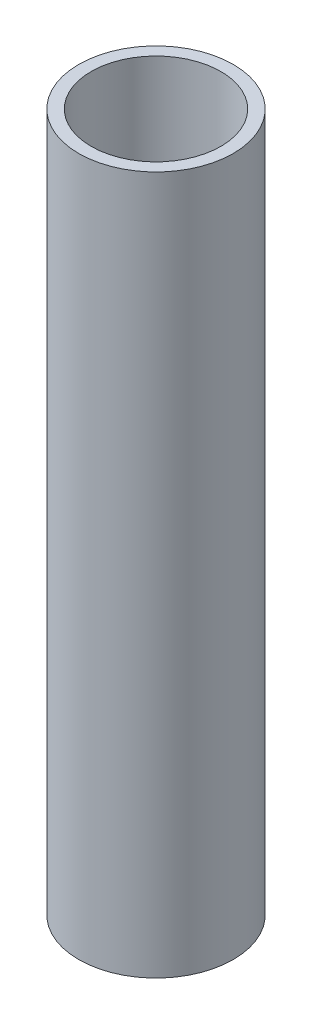
SolidWorks part; units mm, degrees
ref_plane "Front Plane" through (0, 0, 0) normal (0, 0, 1) x (1, 0, 0)
ref_plane "Top Plane" through (0, 0, 0) normal (0, 1, 0) x (1, 0, 0)
ref_plane "Right Plane" through (0, 0, 0) normal (1, 0, 0) x (0, 0, -1)
sketch "Sketch1" plane through (0, 0, 0) normal (0, 1, 0) x (1, 0, 0)
  circle A0 centre (0, 0) radius 12.5
  circle A1 centre (0, 0) radius 10.5
  dimension "D1" = 25
  dimension "D2" = 21
extrude "Boss-Extrude1" add sketch "Sketch1" along normal blind 113
equation "\"cf_tube_outer_diameter\" = 25mm"
equation "\"cf_tube_inner_diameter\" = 21mm"
equation "\"mid_plate_mid_to_top\" = 100mm"
equation "\"mid_plate_mid_to_bottom\" = 30mm"
equation "\"mid_plate_horizontal_spacing\" = 250mm"
equation "\"cf_plate_thickness\" = 3mm"
equation "\"mid_tube_length\" = 500mm"
equation "\"D1@Sketch1\"=\"cf_tube_outer_diameter\""
equation "\"D2@Sketch1\"=\"cf_tube_inner_diameter\""
